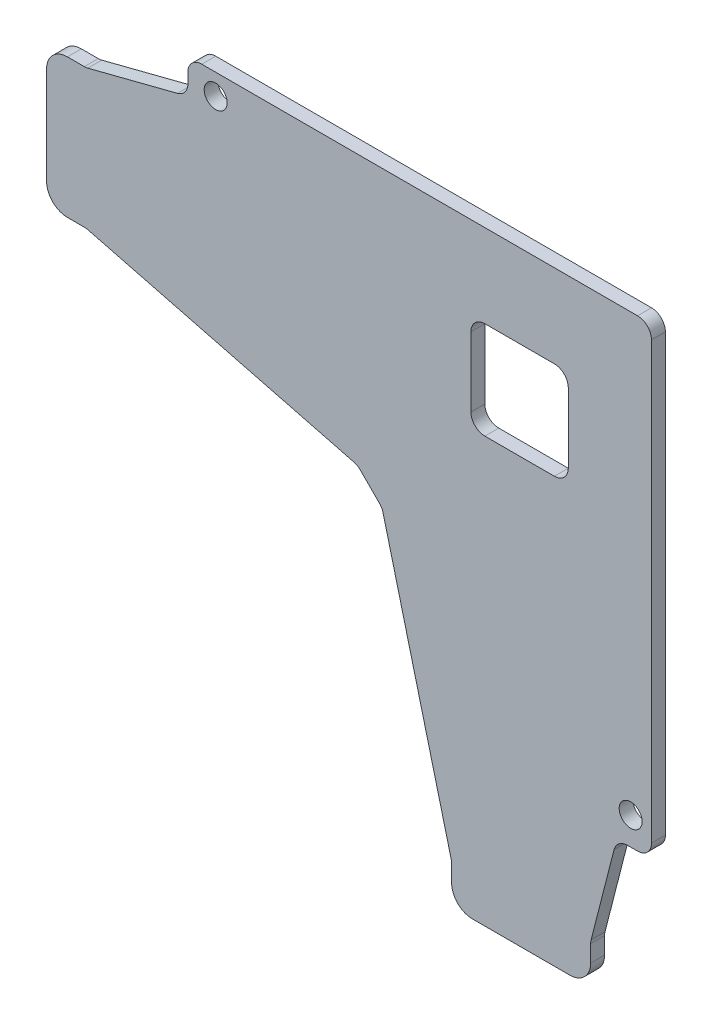
SolidWorks part; units mm, degrees
ref_plane "Front Plane" through (0, 0, 0) normal (0, 0, 1) x (1, 0, 0)
ref_plane "Top Plane" through (0, 0, 0) normal (0, 1, 0) x (1, 0, 0)
ref_plane "Right Plane" through (0, 0, 0) normal (1, 0, 0) x (0, 0, -1)
sketch "Sketch1" plane through (0, 0, 0) normal (0, 0, 1) x (1, 0, 0)
  line L0 (-86, -7.75) -> (-86, -27.75)
  line L1 (-27.75, -86) -> (-7.75, -86)
  line L2 (-86, -7.75) -> (-95.5, -7.75) construction
  line L3 (-86, -27.75) -> (-80.5674, -27.75)
  line L4 (-27.75, -86) -> (-27.75, -95.5) construction
  line L5 (-7.75, -86) -> (-7.75, -80.5674)
  line L23 (-10.25, -92) -> (-10.25, -95.5)
  line L24 (-10.25, -95.5) -> (-7.75, -95.5)
  line L25 (-7.75, -95.5) -> (-7.75, -80.5674)
  line L26 (-7.6874, -80.0709) -> (-4.3853, -67.1846)
  line L27 (-2.4479, -65.6811) -> (-1, -65.6811)
  line L28 (1, -63.6811) -> (1, -1)
  line L29 (-1, 1) -> (-63.6811, 1)
  line L30 (-65.6811, -1) -> (-65.6811, -2.4479)
  line L31 (-67.1846, -4.3853) -> (-80.0709, -7.6874)
  line L32 (-80.5674, -7.75) -> (-95.5, -7.75)
  line L33 (-95.5, -7.75) -> (-95.5, -10.25)
  line L34 (-95.5, -10.25) -> (-92, -10.25)
  line L35 (-90, -12.25) -> (-90, -23.25)
  line L36 (-92, -25.25) -> (-95.5, -25.25)
  line L37 (-95.5, -25.25) -> (-95.5, -27.75)
  line L38 (-95.5, -27.75) -> (-80.5674, -27.75)
  line L39 (-80.0709, -27.8126) -> (-41.8142, -37.6159)
  line L40 (-40.8965, -38.1391) -> (-38.1391, -40.8965)
  line L41 (-37.6159, -41.8142) -> (-27.8126, -80.0709)
  line L42 (-27.75, -80.5674) -> (-27.75, -95.5)
  line L43 (-27.75, -95.5) -> (-25.25, -95.5)
  line L44 (-25.25, -95.5) -> (-25.25, -92)
  line L45 (-23.25, -90) -> (-12.25, -90)
  line L46 (-10.25, -92) -> (-10.25, -95.5) construction
  line L47 (-10.25, -95.5) -> (-7.75, -95.5) construction
  line L48 (-7.75, -95.5) -> (-7.75, -86) construction
  line L49 (-7.6874, -80.0709) -> (-4.3853, -67.1846)
  line L50 (-2.4479, -65.6811) -> (-1, -65.6811)
  line L51 (1, -63.6811) -> (1, -1)
  line L52 (-1, 1) -> (-63.6811, 1)
  line L53 (-65.6811, -1) -> (-65.6811, -2.4479)
  line L54 (-67.1846, -4.3853) -> (-80.0709, -7.6874)
  line L55 (-80.5674, -7.75) -> (-86, -7.75)
  line L56 (-95.5, -7.75) -> (-95.5, -10.25) construction
  line L57 (-95.5, -10.25) -> (-92, -10.25) construction
  line L58 (-90, -12.25) -> (-90, -23.25) construction
  line L59 (-92, -25.25) -> (-95.5, -25.25) construction
  line L60 (-95.5, -25.25) -> (-95.5, -27.75) construction
  line L61 (-95.5, -27.75) -> (-86, -27.75) construction
  line L62 (-80.0709, -27.8126) -> (-41.8142, -37.6159)
  line L63 (-40.8965, -38.1391) -> (-38.1391, -40.8965)
  line L64 (-37.6159, -41.8142) -> (-27.8126, -80.0709)
  line L65 (-27.75, -80.5674) -> (-27.75, -86)
  line L66 (-27.75, -95.5) -> (-25.25, -95.5) construction
  line L67 (-25.25, -95.5) -> (-25.25, -92) construction
  line L68 (-23.25, -90) -> (-12.25, -90) construction
  arc A15 (-7.6874, -80.0709) -> (-7.75, -80.5674) centre (-5.75, -80.5674) ccw
  arc A16 (-2.4479, -65.6811) -> (-4.3853, -67.1846) centre (-2.4479, -67.6811) ccw
  arc A17 (-1, -65.6811) -> (1, -63.6811) centre (-1, -63.6811) ccw
  arc A18 (1, -1) -> (-1, 1) centre (-1, -1) ccw
  arc A19 (-63.6811, 1) -> (-65.6811, -1) centre (-63.6811, -1) ccw
  arc A20 (-67.1846, -4.3853) -> (-65.6811, -2.4479) centre (-67.6811, -2.4479) ccw
  arc A21 (-80.5674, -7.75) -> (-80.0709, -7.6874) centre (-80.5674, -5.75) ccw
  arc A22 (-90, -12.25) -> (-92, -10.25) centre (-92, -12.25) ccw
  arc A23 (-92, -25.25) -> (-90, -23.25) centre (-92, -23.25) ccw
  arc A24 (-80.0709, -27.8126) -> (-80.5674, -27.75) centre (-80.5674, -29.75) ccw
  arc A25 (-40.8965, -38.1391) -> (-41.8142, -37.6159) centre (-42.3107, -39.5533) ccw
  arc A26 (-37.6159, -41.8142) -> (-38.1391, -40.8965) centre (-39.5533, -42.3107) ccw
  arc A27 (-27.75, -80.5674) -> (-27.8126, -80.0709) centre (-29.75, -80.5674) ccw
  arc A28 (-23.25, -90) -> (-25.25, -92) centre (-23.25, -92) ccw
  arc A29 (-10.25, -92) -> (-12.25, -90) centre (-12.25, -92) ccw
  arc A30 (-7.6874, -80.0709) -> (-7.75, -80.5674) centre (-5.75, -80.5674) ccw
  arc A31 (-2.4479, -65.6811) -> (-4.3853, -67.1846) centre (-2.4479, -67.6811) ccw
  arc A32 (-1, -65.6811) -> (1, -63.6811) centre (-1, -63.6811) ccw
  arc A33 (1, -1) -> (-1, 1) centre (-1, -1) ccw
  arc A34 (-63.6811, 1) -> (-65.6811, -1) centre (-63.6811, -1) ccw
  arc A35 (-67.1846, -4.3853) -> (-65.6811, -2.4479) centre (-67.6811, -2.4479) ccw
  arc A36 (-80.5674, -7.75) -> (-80.0709, -7.6874) centre (-80.5674, -5.75) ccw
  arc A37 (-90, -12.25) -> (-92, -10.25) centre (-92, -12.25) ccw construction
  arc A38 (-92, -25.25) -> (-90, -23.25) centre (-92, -23.25) ccw construction
  arc A39 (-80.0709, -27.8126) -> (-80.5674, -27.75) centre (-80.5674, -29.75) ccw
  arc A40 (-40.8965, -38.1391) -> (-41.8142, -37.6159) centre (-42.3107, -39.5533) ccw
  arc A41 (-37.6159, -41.8142) -> (-38.1391, -40.8965) centre (-39.5533, -42.3107) ccw
  arc A42 (-27.75, -80.5674) -> (-27.8126, -80.0709) centre (-29.75, -80.5674) ccw
  arc A43 (-23.25, -90) -> (-25.25, -92) centre (-23.25, -92) ccw construction
  arc A44 (-10.25, -92) -> (-12.25, -90) centre (-12.25, -92) ccw construction
  dimension "D2" = 4
  dimension "D3" = 4
  dimension "D1" = 0
sketch "Sketch2" plane through (0, 0, 0) normal (0, 0, 1) x (1, 0, 0)
  circle A0 centre (-61.6811, -2) radius 1.65 construction
  circle A1 centre (-2, -61.6811) radius 1.65 construction
  circle A2 centre (-61.6811, -2) radius 1.65
  circle A3 centre (-2, -61.6811) radius 1.65
sketch "Sketch4" plane through (0, 0, 0) normal (0, 0, 1) x (1, 0, 0)
  line L0 (-24.9687, -12.9687) -> (-24.9687, -22.9687) construction
  line L1 (-12.9687, -10.9687) -> (-22.9687, -10.9687) construction
  line L2 (-10.9687, -22.9687) -> (-10.9687, -12.9687) construction
  line L3 (-22.9687, -24.9687) -> (-12.9687, -24.9687) construction
  line L4 (-24.9687, -12.9687) -> (-24.9687, -22.9687)
  line L5 (-12.9687, -10.9687) -> (-22.9687, -10.9687)
  line L6 (-10.9687, -22.9687) -> (-10.9687, -12.9687)
  line L7 (-22.9687, -24.9687) -> (-12.9687, -24.9687)
  arc A1 (-24.9687, -22.9687) -> (-22.9687, -24.9687) centre (-22.9687, -22.9687) ccw construction
  arc A2 (-22.9687, -10.9687) -> (-24.9687, -12.9687) centre (-22.9687, -12.9687) ccw construction
  arc A3 (-10.9687, -12.9687) -> (-12.9687, -10.9687) centre (-12.9687, -12.9687) ccw construction
  arc A4 (-12.9687, -24.9687) -> (-10.9687, -22.9687) centre (-12.9687, -22.9687) ccw construction
  arc A5 (-24.9687, -22.9687) -> (-22.9687, -24.9687) centre (-22.9687, -22.9687) ccw
  arc A6 (-22.9687, -10.9687) -> (-24.9687, -12.9687) centre (-22.9687, -12.9687) ccw
  arc A7 (-10.9687, -12.9687) -> (-12.9687, -10.9687) centre (-12.9687, -12.9687) ccw
  arc A8 (-12.9687, -24.9687) -> (-10.9687, -22.9687) centre (-12.9687, -22.9687) ccw
extrude "Boss-Extrude1" add sketch "Sketch1" along normal blind 2
extrude "Cut-Extrude2" cut sketch "Sketch4" along normal through all
sketch "Sketch5" plane through (0, 0, 0) normal (0, 0, 1) x (1, 0, 0)
  line L0 (-78.4965, -9.8647) -> (-46.0979, -1.5626) construction
  line L1 (-78.4965, -9.8647) -> (-46.0979, -1.5626) construction
  line L2 (-80, -11.8021) -> (-80, -23.6979) construction
  line L3 (-40.5305, -35.3641) -> (-78.4965, -25.6353) construction
  line L4 (-35.8872, -39.6128) -> (-39.6128, -35.8872) construction
  line L5 (-25.6353, -78.4965) -> (-35.3641, -40.5305) construction
  line L6 (-23.6979, -80) -> (-11.8021, -80) construction
  line L7 (-1.5626, -46.0979) -> (-9.8647, -78.4965) construction
  line L8 (-1.5, -3.5) -> (-1.5, -45.6015) construction
  line L9 (-45.6015, -1.5) -> (-3.5, -1.5) construction
  line L10 (-80, -11.8021) -> (-80, -23.6979) construction
  line L11 (-40.5305, -35.3641) -> (-78.4965, -25.6353) construction
  line L12 (-35.8872, -39.6128) -> (-39.6128, -35.8872) construction
  line L13 (-25.6353, -78.4965) -> (-35.3641, -40.5305) construction
  line L14 (-23.6979, -80) -> (-11.8021, -80) construction
  line L15 (-1.5626, -46.0979) -> (-9.8647, -78.4965) construction
  line L16 (-1.5, -3.5) -> (-1.5, -45.6015) construction
  line L17 (-45.6015, -1.5) -> (-3.5, -1.5) construction
  line L18 (-78.4468, -10.0585) -> (-46.0483, -1.7563)
  line L19 (-45.6015, -1.7) -> (-3.5, -1.7)
  line L20 (-1.7, -3.5) -> (-1.7, -45.6015)
  line L21 (-1.7563, -46.0483) -> (-10.0585, -78.4468)
  line L22 (-23.6979, -79.8) -> (-11.8021, -79.8)
  line L23 (-25.4415, -78.4468) -> (-35.1703, -40.4809)
  line L24 (-35.7458, -39.4713) -> (-39.4713, -35.7458)
  line L25 (-40.4809, -35.1703) -> (-78.4468, -25.4415)
  line L26 (-79.8, -11.8021) -> (-79.8, -23.6979)
  line L27 (-77.8, -11.9573) -> (-77.8, -23.5427)
  line L28 (-39.9844, -33.2329) -> (-77.8, -23.5427)
  line L29 (-34.3316, -38.0571) -> (-38.0571, -34.3316)
  line L30 (-23.5427, -77.8) -> (-33.2329, -39.9844)
  line L31 (-23.5427, -77.8) -> (-11.9573, -77.8)
  line L32 (-3.7, -45.5763) -> (-11.9573, -77.8)
  line L33 (-3.7, -3.7) -> (-3.7, -45.5763)
  line L34 (-45.5763, -3.7) -> (-3.7, -3.7)
  line L35 (-77.8, -11.9573) -> (-45.5763, -3.7)
  arc A0 (-78.4965, -9.8647) -> (-80, -11.8021) centre (-78, -11.8021) ccw construction
  arc A1 (-80, -23.6979) -> (-78.4965, -25.6353) centre (-78, -23.6979) ccw construction
  arc A2 (-39.6128, -35.8872) -> (-40.5305, -35.3641) centre (-41.027, -37.3015) ccw construction
  arc A3 (-25.6353, -78.4965) -> (-23.6979, -80) centre (-23.6979, -78) ccw construction
  arc A4 (-11.8021, -80) -> (-9.8647, -78.4965) centre (-11.8021, -78) ccw construction
  arc A5 (-1.5626, -46.0979) -> (-1.5, -45.6015) centre (-3.5, -45.6015) ccw construction
  arc A6 (-1.5, -3.5) -> (-3.5, -1.5) centre (-3.5, -3.5) ccw construction
  arc A7 (-45.6015, -1.5) -> (-46.0979, -1.5626) centre (-45.6015, -3.5) ccw construction
  arc A8 (-78.4965, -9.8647) -> (-80, -11.8021) centre (-78, -11.8021) ccw construction
  arc A9 (-80, -23.6979) -> (-78.4965, -25.6353) centre (-78, -23.6979) ccw construction
  arc A10 (-39.6128, -35.8872) -> (-40.5305, -35.3641) centre (-41.027, -37.3015) ccw construction
  arc A11 (-25.6353, -78.4965) -> (-23.6979, -80) centre (-23.6979, -78) ccw construction
  arc A12 (-11.8021, -80) -> (-9.8647, -78.4965) centre (-11.8021, -78) ccw construction
  arc A13 (-1.5626, -46.0979) -> (-1.5, -45.6015) centre (-3.5, -45.6015) ccw construction
  arc A14 (-1.5, -3.5) -> (-3.5, -1.5) centre (-3.5, -3.5) ccw construction
  arc A15 (-45.6015, -1.5) -> (-46.0979, -1.5626) centre (-45.6015, -3.5) ccw construction
  arc A16 (-45.6015, -1.7) -> (-46.0483, -1.7563) centre (-45.6015, -3.5) ccw
  arc A17 (-1.7, -3.5) -> (-3.5, -1.7) centre (-3.5, -3.5) ccw
  arc A18 (-1.7563, -46.0483) -> (-1.7, -45.6015) centre (-3.5, -45.6015) ccw
  arc A19 (-11.8021, -79.8) -> (-10.0585, -78.4468) centre (-11.8021, -78) ccw
  arc A20 (-25.4415, -78.4468) -> (-23.6979, -79.8) centre (-23.6979, -78) ccw
  arc A21 (-35.1703, -40.4809) -> (-35.7458, -39.4713) centre (-37.3015, -41.027) ccw
  arc A22 (-39.4713, -35.7458) -> (-40.4809, -35.1703) centre (-41.027, -37.3015) ccw
  arc A23 (-79.8, -23.6979) -> (-78.4468, -25.4415) centre (-78, -23.6979) ccw
  arc A24 (-35.3641, -40.5305) -> (-35.8872, -39.6128) centre (-37.3015, -41.027) ccw construction
  arc A25 (-35.3641, -40.5305) -> (-35.8872, -39.6128) centre (-37.3015, -41.027) ccw construction
  arc A26 (-78.4468, -10.0585) -> (-79.8, -11.8021) centre (-78, -11.8021) ccw
  arc A27 (-77.8, -23.5427) -> (-77.8, -23.5427) centre (-77.8, -23.5427) ccw
  arc A28 (-38.0571, -34.3316) -> (-39.9844, -33.2329) centre (-41.027, -37.3015) ccw
  arc A29 (-33.2329, -39.9844) -> (-34.3316, -38.0571) centre (-37.3015, -41.027) ccw
  arc A30 (-23.5427, -77.8) -> (-23.5427, -77.8) centre (-23.5427, -77.8) ccw
  arc A31 (-11.9573, -77.8) -> (-11.9573, -77.8) centre (-11.9573, -77.8) ccw
  arc A32 (-3.7, -45.5763) -> (-3.7, -45.5763) centre (-3.7, -45.5763) ccw
  arc A33 (-3.7, -3.7) -> (-3.7, -3.7) centre (-3.7, -3.7) ccw
  arc A34 (-45.5763, -3.7) -> (-45.5763, -3.7) centre (-45.5763, -3.7) ccw
  arc A35 (-77.8, -11.9573) -> (-77.8, -11.9573) centre (-77.8, -11.9573) ccw
  dimension "D1" = 0.2
  dimension "D2" = 2.2
extrude "Boss-Extrude2" add sketch "Sketch5" against normal blind 1.2
chamfer "Chamfer1" distance 1.2 angle 45 11 edges at (-28.3878, -58.8922, 0) (-33.6527, -38.9469, 0) (-36.1944, -36.1944, 0) (-38.9469, -33.6527, 0) (-17.75, -77.8, 0) (-7.8287, -61.6881, 0) (-3.7, -24.6381, 0) (-24.6381, -3.7, 0) (-61.6881, -7.8287, 0) (-77.8, -17.75, 0) (-58.8922, -28.3878, 0)
extrude "Cut-Extrude3" cut sketch "Sketch2" along normal through all
fillet "Fillet1" radius 3 4 edges at (-27.75, -86, 1) (-7.75, -86, 1) (-86, -7.75, 1) (-86, -27.75, 1)
